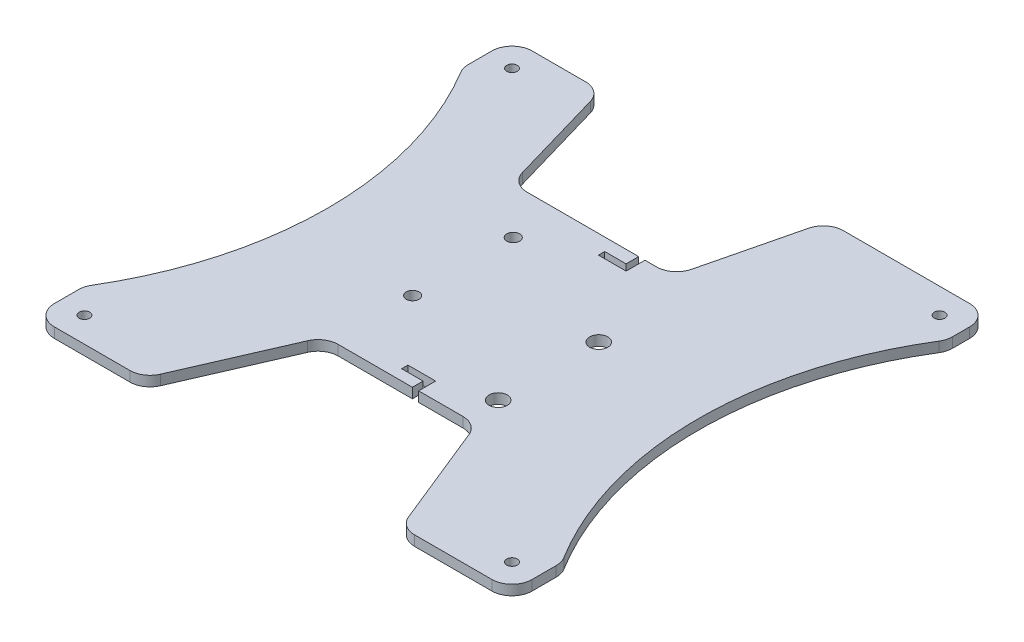
SolidWorks part; units mm, degrees
ref_plane "Front Plane" through (0, 0, 0) normal (0, 0, 1) x (1, 0, 0)
ref_plane "Top Plane" through (0, 0, 0) normal (0, 1, 0) x (1, 0, 0)
ref_plane "Right Plane" through (0, 0, 0) normal (1, 0, 0) x (0, 0, -1)
sketch "Sketch1" plane through (0, 0, 0) normal (0, 1, 0) x (1, 0, 0)
  line L0 (-95, 0) -> (95, 0) construction
  line L1 (-95, 95) -> (95, 95)
  line L2 (-95, 95) -> (-95, -95)
  line L3 (-95, -95) -> (95, -95)
  line L4 (95, 95) -> (95, -95)
  line L5 (-95, 95) -> (95, -95) construction
  line L6 (-95, -95) -> (95, 95) construction
  line L7 (0, 95) -> (0, -95) construction
  circle A0 centre (-85, 85) radius 2.1
  point P0 (0, 0)
  dimension "D3" = 4.2
  dimension "D1" = 190
  dimension "D2" = 190
  dimension "D4" = 85
extrude "base" add sketch "Sketch1" against normal blind 4 contours L2 L3 L4 L1
extrude "Cut-Extrude2" cut sketch "Sketch1<5>" against normal blind 4 contours A0
sketch "Sketch1<5>" plane through (0, 0, 0) normal (0, 1, 0) x (1, 0, 0) same geometry as "Sketch1"
mirror "Mirror1" about plane through (0, 0, 0) normal (1, 0, 0) of "Cut-Extrude2"
mirror "Mirror2" about plane through (0, 0, 0) normal (0, 0, 1) of "Cut-Extrude2", "Mirror1"
sketch "Sketch2" plane through (0, 0, 0) normal (0, 1, 0) x (1, 0, 0)
  line L0 (-95, 0) -> (95, 0) construction
  line L1 (0, 95) -> (0, -95) construction
  circle A0 centre (-26.5, 27) radius 2.55
  circle A1 centre (-26.5, -13) radius 2.55
  circle A2 centre (26.5, -32) radius 3.6
  circle A3 centre (26.5, 8) radius 3.6
  dimension "D3" = 5.1
  dimension "D4" = 5.1
  dimension "D7" = 7.2
  dimension "D8" = 7.2
  dimension "D1" = 27
  dimension "D5" = 13
  dimension "D6" = 26.5
  dimension "D9" = 8
  dimension "D11" = 32
  dimension "D12" = 26.5
extrude "holes" cut sketch "Sketch2" against normal through all
sketch "Sketch3" plane through (0, 0, 0) normal (0, 1, 0) x (1, 0, 0)
  line L0 (0, 45.3666) -> (-45.3666, 45.3666)
  line L1 (0, 95) -> (0, -95) construction
  line L2 (-59.7327, 95) -> (-45.3666, 45.3666)
  line L3 (-95, 95) -> (95, 95) construction
  line L4 (-95, 95) -> (95, -95) construction
  line L5 (-59.7327, 95) -> (-95, 95)
  line L6 (-95, 95) -> (-95, 76.1151)
  line L7 (-95, 95) -> (-95, -95) construction
  line L8 (-95, 76.1151) -> (-95, -95)
  line L9 (-95, -95) -> (-51.6676, -95)
  line L10 (-95, -95) -> (95, -95) construction
  line L11 (-51.6676, -95) -> (-29.7404, -44.6105)
  line L12 (-29.7404, -44.6105) -> (30.4965, -44.6105)
  line L13 (30.4965, -44.6105) -> (50.9115, -95)
  line L14 (50.9115, -95) -> (95, -95)
  line L15 (95, -95) -> (95, 95)
  line L16 (95, 95) -> (30.4965, 95)
  line L17 (30.4965, 95) -> (18.3987, 45.3666)
  line L18 (18.3987, 45.3666) -> (0, 45.3666)
  line L19 (-59.7327, 95) -> (30.4965, 95)
  line L20 (-51.6676, -95) -> (50.9115, -95)
  line M9 (95, 95) -> (-95, 95)
  line M11 (-95, -95) -> (95, -95)
extrude "Cut-Extrude4" cut sketch "Sketch3" against normal blind 4 contours L18 L17 L2 L0 M9 | L13 L12 L11 M11 region at (-14.0835, 0, -71.6049) region at (-0.0328, 0, 71.9893)
sketch "Sketch5" plane through (0, 0, 0) normal (0, 1, 0) x (1, 0, 0)
  line L0 (-95, 95) -> (-95, -95) construction
  line L1 (95, 95) -> (95, -95) construction
  line L2 (-95, 75.359) -> (-95, -75.107)
  line L3 (95, -75.107) -> (95, 77.8794)
  arc A0 (-95, 75.359) -> (-95, -75.107) centre (-215.9061, 0.126) cw
  arc A1 (95, 77.8794) -> (95, -75.107) centre (214.8002, 1.3862) ccw
extrude "Cut-Extrude5" cut sketch "Sketch5" against normal blind 4 contours A0 L2
extrude "Cut-Extrude6" cut sketch "Sketch5<3>" against normal blind 4
sketch "Sketch5<3>" plane through (0, 0, 0) normal (0, 1, 0) x (1, 0, 0) same geometry as "Sketch5"
fillet "Fillet1" radius 8 16 edges at (-95, -2, 75.107) (-95, -2, 95) (-51.6676, -2, 95) (-29.7404, -2, 44.6105) (30.4965, -2, 44.6105) (50.9115, -2, 95) (95, -2, 95) (95, -2, 75.107) (95, -2, -77.8794) (95, -2, -95) (30.4965, -2, -95) (18.3987, -2, -45.3666) (-45.3666, -2, -45.3666) (-59.7327, -2, -95) (-95, -2, -75.359) (-95, -2, -95)
sketch "Sketch7" plane through (0, 0, 0) normal (0, 1, 0) x (1, 0, 0)
  line L0 (5, 45.3666) -> (5, 40.3666)
  line L1 (12.1144, 45.3666) -> (-39.3538, 45.3666) construction
  line L2 (5, 40.3666) -> (-3.5, 40.3666)
  line L3 (-3.5, 40.3666) -> (-3.5, 37.8666)
  line L4 (-3.5, 37.8666) -> (7.5, 37.8666)
  line L5 (7.5, 37.8666) -> (7.5, 45.3666)
  line L6 (7.5, 45.3666) -> (5, 45.3666)
  line L7 (0, 95) -> (0, -95) construction
  dimension "D1" = 2.5
  dimension "D2" = 7.5
  dimension "D3" = 2.5
  dimension "D4" = 11
  dimension "D5" = 7.5
extrude "Cut-Extrude7" cut sketch "Sketch7" against normal blind 4
mirror "Mirror3" about plane through (0, 0, 0) normal (0, 0, 1) of "Cut-Extrude7"
